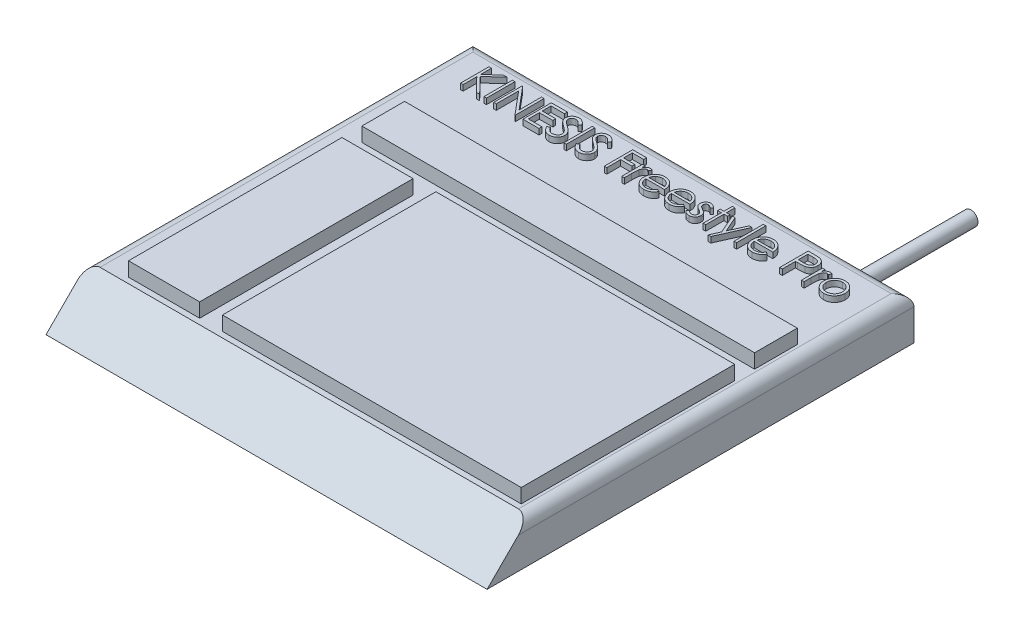
SolidWorks part; units mm, degrees
ref_plane "Front Plane" through (0, 0, 0) normal (0, 0, 1) x (1, 0, 0)
ref_plane "Top Plane" through (0, 0, 0) normal (0, 1, 0) x (1, 0, 0)
ref_plane "Right Plane" through (0, 0, 0) normal (1, 0, 0) x (0, 0, -1)
sketch "Sketch1" plane through (0, 0, 0) normal (0, 1, 0) x (1, 0, 0)
  line L1 (0, 0) -> (196.85, 0)
  line L2 (0, 0) -> (0, -165.1)
  line L3 (0, -165.1) -> (196.85, -165.1)
  line L4 (196.85, 0) -> (196.85, -165.1)
  point P7 (0, 0)
  dimension "D1" = 165.1
  dimension "D3" = 196.85
extrude "Boss-Extrude1" add sketch "Sketch1" along normal blind 19.05
sketch "Sketch2" plane through (0, 0, 0) normal (0, 1, 0) x (1, 0, 0)
  line L0 (0, -165.1) -> (196.85, -165.1)
  line L1 (0, -165.1) -> (0, -190.5)
  line L2 (196.85, -165.1) -> (196.85, -190.5)
  line L3 (0, -190.5) -> (196.85, -190.5)
  dimension "D1" = 25.4
extrude "Boss-Extrude2" add sketch "Sketch2" along normal blind 19.05 contours L0 L1 L3 L2
chamfer "Chamfer1" distance 19.05 angle 45 1 edges at (98.425, 19.05, 190.5)
sketch "Sketch3" plane through (0, 19.05, 0) normal (0, 1, 0) x (1, 0, 0)
  line L0 (196.85, -171.45) -> (196.85, 0) construction
  line L1 (15.24, -168.91) -> (46.99, -168.91)
  line L2 (15.24, -168.91) -> (15.24, -73.66)
  line L3 (15.24, -73.66) -> (46.99, -73.66)
  line L4 (46.99, -168.91) -> (46.99, -73.66)
  line L5 (57.15, -168.91) -> (190.5, -168.91)
  line L6 (57.15, -168.91) -> (57.15, -73.66)
  line L7 (57.15, -73.66) -> (190.5, -73.66)
  line L8 (190.5, -168.91) -> (190.5, -73.66)
  line L9 (0, -171.45) -> (196.85, -171.45) construction
  line L10 (0, 0) -> (0, -171.45) construction
  line L11 (15.24, -45.72) -> (190.5, -45.72)
  line L12 (15.24, -45.72) -> (15.24, -64.77)
  line L13 (15.24, -64.77) -> (190.5, -64.77)
  line L14 (190.5, -45.72) -> (190.5, -64.77)
  dimension "D1" = 6.35
  dimension "D2" = 133.35
  dimension "D3" = 2.54
  dimension "D4" = 95.25
  dimension "D5" = 2.54
  dimension "D6" = 31.75
  dimension "D7" = 10.16
  dimension "D8" = 95.25
  dimension "D9" = 6.35
  dimension "D10" = 15.24
  dimension "D11" = 8.89
  dimension "D12" = 19.05
extrude "Boss-Extrude3" add sketch "Sketch3" along normal blind 6.35
sketch "Sketch4" plane through (0, 19.05, 0) normal (0, 1, 0) x (1, 0, 0)
  line L0 (15.24, -45.72) -> (15.24, -64.77) construction
  text T0 "KINESIS Freestyle Pro" font "Century Gothic" height 12.7
  dimension "D1" = 0
extrude "Boss-Extrude4" add sketch "Sketch4" along normal blind 2.54
sketch "Sketch5" plane through (0, 0, 0) normal (0, 0, -1) x (-1, 0, 0)
  line L0 (-196.85, 19.05) -> (0, 19.05) construction
  line L1 (-196.85, 19.05) -> (-196.85, 0) construction
  circle A0 centre (-171.45, 10.16) radius 3.175
  dimension "D3" = 6.35
  dimension "D1" = 8.89
  dimension "D2" = 25.4
extrude "Boss-Extrude5" add sketch "Sketch5" along normal blind 50.8
fillet "Fillet1" radius 5.08 3 edges at (98.425, 19.05, 0) (0, 19.05, 85.725) (196.85, 19.05, 85.725)
sketch "Sketch6" plane through (0, 0, 0) normal (0, -1, 0) x (1, 0, 0)
  line L0 (25.4, 179.07) -> (12.7, 179.07) construction
  line L1 (25.4, 172.72) -> (12.7, 172.72)
  line L2 (25.4, 185.42) -> (12.7, 185.42)
  line L3 (0, 190.5) -> (196.85, 190.5) construction
  line L4 (0, 0) -> (0, 190.5) construction
  line L5 (98.425, 190.5) -> (98.425, 55.114) construction
  line L6 (0, 95.25) -> (246.7978, 95.25) construction
  line L7 (171.45, 179.07) -> (184.15, 179.07) construction
  line L8 (171.45, 172.72) -> (184.15, 172.72)
  line L9 (171.45, 185.42) -> (184.15, 185.42)
  line L10 (171.45, 11.43) -> (184.15, 11.43) construction
  line L11 (171.45, 17.78) -> (184.15, 17.78)
  line L12 (171.45, 5.08) -> (184.15, 5.08)
  line L13 (25.4, 11.43) -> (12.7, 11.43) construction
  line L14 (25.4, 17.78) -> (12.7, 17.78)
  line L15 (25.4, 5.08) -> (12.7, 5.08)
  arc A0 (25.4, 172.72) -> (25.4, 185.42) centre (25.4, 179.07) ccw
  arc A1 (12.7, 185.42) -> (12.7, 172.72) centre (12.7, 179.07) ccw
  arc A2 (171.45, 172.72) -> (171.45, 185.42) centre (171.45, 179.07) cw
  arc A3 (184.15, 185.42) -> (184.15, 172.72) centre (184.15, 179.07) cw
  arc A4 (171.45, 17.78) -> (171.45, 5.08) centre (171.45, 11.43) ccw
  arc A5 (184.15, 5.08) -> (184.15, 17.78) centre (184.15, 11.43) ccw
  arc A6 (25.4, 17.78) -> (25.4, 5.08) centre (25.4, 11.43) cw
  arc A7 (12.7, 5.08) -> (12.7, 17.78) centre (12.7, 11.43) cw
  point P2 (19.05, 179.07)
  point P17 (177.8, 179.07)
  point P24 (177.8, 11.43)
  point P31 (19.05, 11.43)
  dimension "D1" = 6.35
  dimension "D2" = 12.7
  dimension "D3" = 5.08
  dimension "D4" = 19.05
extrude "Boss-Extrude6" add sketch "Sketch6" along normal blind 2.54
